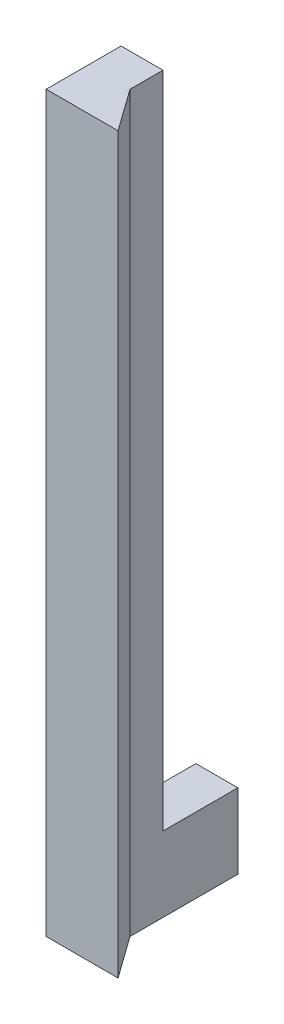
SolidWorks part; units mm, degrees
ref_plane "Front Plane" through (0, 0, 0) normal (0, 0, 1) x (1, 0, 0)
ref_plane "Top Plane" through (0, 0, 0) normal (0, 1, 0) x (1, 0, 0)
ref_plane "Right Plane" through (0, 0, 0) normal (1, 0, 0) x (0, 0, -1)
sketch "Sketch1" plane through (0, 0, 0) normal (0, 1, 0) x (1, 0, 0)
  line L0 (-1.4, -2.5) -> (3.4, -2.5)
  line L1 (-1.4, 2.5) -> (1.4, 2.5)
  line L2 (-1.4, 2.5) -> (-1.4, -2.5)
  line L3 (-1.4, -2.5) -> (1.4, -2.5)
  line L4 (1.4, 2.5) -> (1.4, -2.5)
  line L5 (3.4, -2.5) -> (1.4, 0.3)
  point P4 (0, 2.5)
  point P6 (-1.4, 0)
  point P7 (0, 0)
  dimension "D1" = 5
  dimension "D2" = 2.8
  dimension "D3" = 2.8
  dimension "D4" = 4.8
extrude "Boss-Extrude1" add sketch "Sketch1" along normal blind 49 contours L0 L5 L4 | L4 L1 L2 L0 region at (0, 0, 0) region at (2.0667, 0, 1.5667)
sketch "Sketch2" plane through (0, 0, -2.5) normal (0, 0, -1) x (-1, 0, 0)
  line L0 (-1.4, 49) -> (-1.4, 0) construction
  line L1 (-1.4, 5) -> (1.4, 5)
  line L2 (-1.4, 5) -> (-1.4, 0)
  line L3 (-1.4, 0) -> (1.4, 0)
  line L4 (1.4, 5) -> (1.4, 0)
  dimension "D1" = 5
extrude "Boss-Extrude2" add sketch "Sketch2" along normal blind 5
